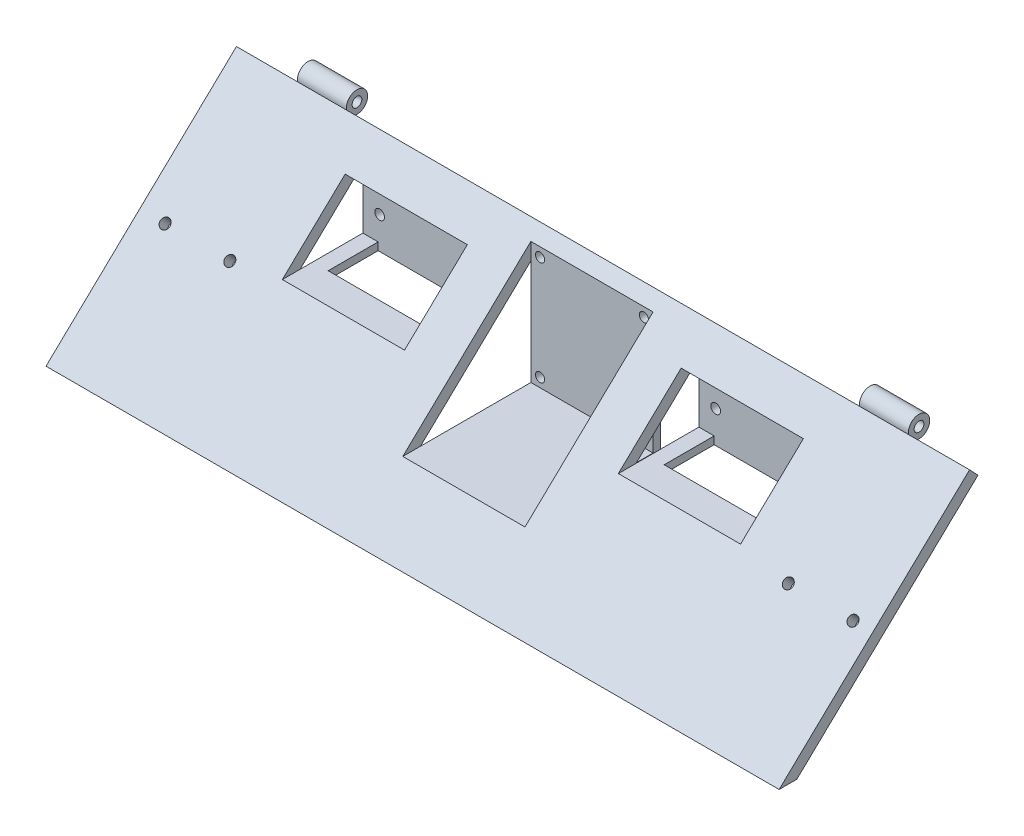
SolidWorks part; units mm, degrees
ref_plane "前视基准面" through (0, 0, 0) normal (0, 0, 1) x (1, 0, 0)
ref_plane "上视基准面" through (0, 0, 0) normal (0, 1, 0) x (1, 0, 0)
ref_plane "右视基准面" through (0, 0, 0) normal (1, 0, 0) x (0, 0, -1)
other "Configuration Table"
sketch "草图1" plane through (0, 0, 0) normal (1, 0, 0) x (0, 0, -1)
  line L0 (0, 0) -> (-23.9796, -22.8749) construction
  line L1 (-62.761, -57.1057) -> (-3.4588, -0.5354)
  line L2 (-62.761, -57.1057) -> (-60, -60)
  line L3 (-3.4588, -0.5354) -> (-0.6978, -3.4297)
  line L4 (-60, -60) -> (-0.6978, -3.4297)
  line L5 (-62.761, -57.1057) -> (-0.6978, -3.4297) construction
  line L6 (-3.4588, -0.5354) -> (-60, -60) construction
  line L7 (-62.761, -57.1057) -> (-65.7951, -60)
  line L8 (-65.7951, -60) -> (-60, -60)
  circle A0 centre (0, 0) radius 3.5
  circle A1 centre (0, 0) radius 1.6
  point P4 (-61.3805, -58.5528)
  point P6 (-31.7294, -30.2677)
  point P7 (-2.0783, -1.9826)
  point P8 (-58.5448, -35.4074)
  point P14 (0, 0)
  point P15 (-47.3852, -40.6579)
  point P16 (-52.4892, -28.6998)
  point P19 (-98.1791, -60)
  dimension "D1" = 3.2
  dimension "D2" = 7
  dimension "D3" = 4
  dimension "D4" = 60
  dimension "D5" = 60
extrude "凸台-拉伸1" add sketch "草图1" along normal blind 120 and the other way blind 120 contours A0 L1 L2 L4 | L7 L8 L2 | L3 A0 region at (0, -30.4148, 31.8836) region at (0, -59.0352, 62.852) region at (0, -2.1573, 2.2615)
extrude "凸台-拉伸2" add sketch "草图1<5>" along normal blind 16 from offset 84 contours L3 A0 A1 region at (0, 3.391, 0.2609)
sketch "草图1<5>" plane through (0, 0, 0) normal (1, 0, 0) x (0, 0, -1) same geometry as "草图1"
mirror "镜向1" about plane through (0, 0, 0) normal (1, 0, 0) of "凸台-拉伸2"
sketch "草图2" plane through (0, 0, 0) normal (1, 0, 0) x (0, 0, -1)
  line L0 (-7.0686, -3.9789) -> (-7.0686, -43.9789)
  line L1 (-7.0686, -43.9789) -> (-49.0003, -43.9789)
  line L2 (-0.6978, -3.4297) -> (-3.6169, -6.2144)
  line L3 (-49.0003, -43.9789) -> (-51.621, -46.4789)
  line L4 (-60, -60) -> (-0.6978, -3.4297)
  line L5 (-0.6978, -3.4297) -> (-3.4588, -0.5354)
  line L6 (-3.4588, -0.5354) -> (-65.7951, -60)
  line L7 (-65.7951, -60) -> (-60, -60)
  line L8 (-60, -60) -> (-0.6978, -3.4297)
  line L9 (-0.6978, -3.4297) -> (-3.4588, -0.5354)
  line L10 (-3.4588, -0.5354) -> (-65.7951, -60)
  line L11 (-65.7951, -60) -> (-60, -60)
  line L12 (-51.621, -46.4789) -> (-4.5686, -46.4789)
  line L13 (-4.5686, -46.4789) -> (-4.5686, -1.5941)
  line L14 (-4.5686, -1.5941) -> (-3.4588, -0.5354)
  point P6 (0, 0)
  point P12 (0, 0)
  dimension "D2" = 40
  dimension "D3" = 2.5
  dimension "D4" = 2.5
  dimension "D1" = 0
extrude "凸台-拉伸3" add sketch "草图2" along normal blind 20 and the other way blind 20 contours L12 L13 L8 L0 L1 region at (0, -8.7272, 5.425)
sketch "草图3" plane through (0, 0, 7.0686) normal (0, 0, 1) x (1, 0, 0)
  line L1 (-20, -43.9789) -> (20, -43.9789)
  line L2 (-20, -43.9789) -> (-20, -3.9789)
  line L3 (-20, -3.9789) -> (20, -3.9789)
  line L4 (-20, -43.9789) -> (20, -43.9789)
  line L5 (20, -43.9789) -> (20, -9.507)
  line L6 (20, -9.507) -> (-20, -9.507)
  line L7 (-20, -9.507) -> (-20, -43.9789)
  line L8 (-20, -43.9789) -> (20, -43.9789)
  line L9 (20, -43.9789) -> (20, -9.507)
  line L10 (20, -9.507) -> (-20, -9.507)
  line L11 (-20, -9.507) -> (-20, -43.9789)
  line L12 (20, -43.9789) -> (20, -3.9789)
  line M7 (-20, -43.9789) -> (20, -43.9789)
  line M8 (20, -43.9789) -> (20, -9.507)
  line M9 (20, -9.507) -> (-20, -9.507)
  line M10 (-20, -9.507) -> (-20, -43.9789)
  dimension "D2" = 40
  dimension "D1" = 0
extrude "切除-拉伸1" cut sketch "草图3" along normal up to surface (41.9317 mm away) contours M10 M7 M8 M9 | L12 L3 L2 M9 region at (0, -26.743, 7.0686) region at (0, -6.743, 7.0686) up to face at (0, -15.4016, 19.0429)
sketch "草图4" plane through (0, 0, 7.0686) normal (0, 0, 1) x (1, 0, 0)
  line L0 (0, -3.9789) -> (0, -43.9789) construction
  line L1 (0, -23.9789) -> (20, -23.9789) construction
  line L6 (-20, -43.9789) -> (20, -43.9789)
  line L7 (20, -43.9789) -> (20, -9.507)
  line L8 (20, -9.507) -> (20, -3.9789)
  line L9 (20, -3.9789) -> (-20, -3.9789)
  line L10 (-20, -3.9789) -> (-20, -9.507)
  line L11 (-20, -9.507) -> (-20, -43.9789)
  line L12 (-20, -43.9789) -> (20, -43.9789)
  line L13 (20, -43.9789) -> (20, -9.507)
  line L14 (20, -9.507) -> (20, -3.9789)
  line L15 (20, -3.9789) -> (-20, -3.9789)
  line L16 (-20, -3.9789) -> (-20, -9.507)
  line L17 (-20, -9.507) -> (-20, -43.9789)
  circle A0 centre (-17, -6.9789) radius 1.5
  circle A1 centre (17, -6.9789) radius 1.5
  circle A2 centre (-17, -40.9789) radius 1.5
  circle A3 centre (17, -40.9789) radius 1.5
  point P20 (14.0664, -3.9789)
  dimension "D2" = 3
  dimension "D3" = 3
  dimension "D4" = 3
  dimension "D1" = 0
extrude "切除-拉伸2" cut sketch "草图4" against normal through all contours A0 | A1 | A3 | A2 region at (-17, -6.9789, 7.0686) region at (17, -6.9789, 7.0686) region at (-17, -40.9789, 7.0686) region at (17, -40.9789, 7.0686)
sketch "草图5" plane through (0, 0, 0) normal (1, 0, 0) x (0, 0, -1)
  line L0 (-60, -60) -> (-0.6978, -3.4297) construction
  line L1 (-60, -60) -> (-0.6978, -3.4297)
  line L2 (-4.5686, -31.6222) -> (-30.2517, -31.6222)
  line L3 (-4.5686, -29.1222) -> (-27.631, -29.1222)
  line L6 (-45.8259, -46.4789) -> (-4.5686, -46.4789)
  line L7 (-4.5686, -46.4789) -> (-4.5686, -7.1222)
  line L8 (-4.5686, -7.1222) -> (-7.0686, -9.507)
  line L9 (-7.0686, -9.507) -> (-7.0686, -43.9789)
  line L10 (-7.0686, -43.9789) -> (-43.2052, -43.9789)
  line L11 (-43.2052, -43.9789) -> (-45.8259, -46.4789)
  line L12 (-45.8259, -46.4789) -> (-4.5686, -46.4789)
  line L13 (-4.5686, -46.4789) -> (-4.5686, -7.1222)
  line L14 (-4.5686, -7.1222) -> (-7.0686, -9.507)
  line L15 (-7.0686, -9.507) -> (-7.0686, -43.9789)
  line L16 (-7.0686, -43.9789) -> (-43.2052, -43.9789)
  line L17 (-43.2052, -43.9789) -> (-45.8259, -46.4789)
  dimension "D2" = 2.5
  dimension "D3" = 22
  dimension "D1" = 0
extrude "凸台-拉伸4" add sketch "草图5" along normal blind 40 from offset 35 contours L15 L3 L1 L2 | L1 L15 L3 L13 | L3 L15 L2 L13 region at (0, -30.3971, 18.0181) region at (0, -30.3722, 5.8186) region at (0, -18.707, 5.7947)
sketch "草图6" plane through (0, 0, 7.0686) normal (0, 0, 1) x (1, 0, 0)
  line L4 (35, -9.507) -> (35, -29.1222)
  line L5 (35, -29.1222) -> (75, -29.1222)
  line L6 (75, -29.1222) -> (75, -9.507)
  line L7 (75, -9.507) -> (35, -9.507)
  line L8 (35, -9.507) -> (35, -29.1222)
  line L9 (35, -29.1222) -> (75, -29.1222)
  line L10 (75, -29.1222) -> (75, -9.507)
  line L11 (75, -9.507) -> (35, -9.507)
  dimension "D1" = 0
extrude "切除-拉伸3" cut sketch "草图6" along normal up to surface (26.3575 mm away) up to face at (0, -15.4016, 19.0429)
sketch "草图7" plane through (0, -29.1222, 0) normal (0, 1, 0) x (1, 0, 0)
  line L1 (40, -7.0686) -> (70, -7.0686)
  line L2 (40, -7.0686) -> (40, -23.4261)
  line L3 (40, -23.4261) -> (70, -23.4261)
  line L4 (70, -7.0686) -> (70, -23.4261)
  line L6 (35, -7.0686) -> (35, -27.631)
  line L7 (35, -27.631) -> (35, -33.4261)
  line L8 (35, -33.4261) -> (75, -33.4261)
  line L9 (75, -33.4261) -> (75, -27.631)
  line L10 (75, -27.631) -> (75, -7.0686)
  line L11 (75, -7.0686) -> (35, -7.0686)
  line L12 (35, -7.0686) -> (35, -27.631)
  line L13 (35, -27.631) -> (35, -33.4261)
  line L14 (35, -33.4261) -> (75, -33.4261)
  line L15 (75, -33.4261) -> (75, -27.631)
  line L16 (75, -27.631) -> (75, -7.0686)
  line L17 (75, -7.0686) -> (35, -7.0686)
  line M15 (75, -7.0686) -> (35, -7.0686)
  dimension "D2" = 5
  dimension "D3" = 5
  dimension "D4" = 10
  dimension "D1" = 0
extrude "切除-拉伸4" cut sketch "草图7" against normal up to surface (2.5 mm away) contours L4 L2 L3 M15 region at (55, -29.1222, 15.2473) up to face at (55, -31.6222, 17.4102)
sketch "草图8" plane through (0, 0, 7.0686) normal (0, 0, 1) x (1, 0, 0)
  line L0 (55, -9.507) -> (55, -31.6222) construction
  line L8 (35, -9.507) -> (35, -29.1222)
  line L9 (35, -29.1222) -> (40, -29.1222)
  line L10 (40, -29.1222) -> (40, -31.6222)
  line L11 (40, -31.6222) -> (70, -31.6222)
  line L12 (70, -31.6222) -> (70, -29.1222)
  line L13 (70, -29.1222) -> (75, -29.1222)
  line L14 (75, -29.1222) -> (75, -9.507)
  line L15 (75, -9.507) -> (35, -9.507)
  line L16 (35, -9.507) -> (35, -29.1222)
  line L17 (35, -29.1222) -> (40, -29.1222)
  line L18 (40, -29.1222) -> (40, -31.6222)
  line L19 (40, -31.6222) -> (70, -31.6222)
  line L20 (70, -31.6222) -> (70, -29.1222)
  line L21 (70, -29.1222) -> (75, -29.1222)
  line L22 (75, -29.1222) -> (75, -9.507)
  line L23 (75, -9.507) -> (35, -9.507)
  circle A0 centre (40.5, -21.1222) radius 1.6
  circle A1 centre (69.5, -21.1222) radius 1.6
  dimension "D2" = 3.2
  dimension "D3" = 29
  dimension "D4" = 8
  dimension "D1" = 0
extrude "切除-拉伸5" cut sketch "草图8" against normal up to surface (2.5 mm away) contours A0 | A1 region at (40.5, -21.1222, 7.0686) region at (69.5, -21.1222, 7.0686) up to face at (55, -19.3722, 4.5686)
mirror "镜向2" about plane through (0, 0, 0) normal (1, 0, 0) of "凸台-拉伸4"
mirror "镜向3" about plane through (0, 0, 0) normal (1, 0, 0) of "切除-拉伸4"
mirror "镜向4" about plane through (0, 0, 0) normal (1, 0, 0) of "切除-拉伸5"
mirror "镜向5" about plane through (0, 0, 0) normal (1, 0, 0) of "切除-拉伸3"
sketch "草图9" plane through (0, -1.4472, -1.3805) normal (0, -0.7236, -0.6902) x (1, 0, 0)
  line L0 (0.9143, 84.8292) -> (0.9143, 2.8723) construction
  line L2 (102.9143, 29.8292) -> (102.9143, 49.8292) construction
  line L3 (118.4143, 29.8292) -> (87.4143, 29.8292) construction
  line L4 (118.4143, 29.8292) -> (118.4143, 49.8292) construction
  line L5 (118.4143, 49.8292) -> (87.4143, 49.8292) construction
  line L6 (87.4143, 29.8292) -> (87.4143, 49.8292) construction
  line L8 (-120, 2.8723) -> (-100, 2.8723)
  line L9 (-100, 2.8723) -> (-84, 2.8723)
  line L10 (-84, 2.8723) -> (84, 2.8723)
  line L11 (84, 2.8723) -> (100, 2.8723)
  line L12 (100, 2.8723) -> (120, 2.8723)
  line L13 (120, 2.8723) -> (120, 84.8292)
  line L14 (120, 84.8292) -> (-120, 84.8292)
  line L15 (-120, 84.8292) -> (-120, 2.8723)
  line L16 (-120, 2.8723) -> (-100, 2.8723)
  line L17 (-100, 2.8723) -> (-84, 2.8723)
  line L18 (-84, 2.8723) -> (84, 2.8723)
  line L19 (84, 2.8723) -> (100, 2.8723)
  line L20 (100, 2.8723) -> (120, 2.8723)
  line L21 (120, 2.8723) -> (120, 84.8292)
  line L22 (120, 84.8292) -> (-120, 84.8292)
  line L23 (-120, 84.8292) -> (-120, 2.8723)
  circle A0 centre (113.5112, 46.6292) radius 1.6
  circle A1 centre (92.3174, 46.6292) radius 1.6
  circle A2 centre (-90.4888, 46.6292) radius 1.6
  circle A3 centre (-111.6826, 46.6292) radius 1.6
  point P20 (75.5314, 63.7755)
  dimension "D4" = 3.2
  dimension "D2" = 31
  dimension "D3" = 20
  dimension "D5" = 3.2
  dimension "D6" = 102
  dimension "D7" = 35
  dimension "D1" = 0
extrude "切除-拉伸6" cut sketch "草图9" against normal up to surface (4 mm away) contours A0 | A1 | A2 | A3 region at (113.5112, -33.6327, 32.3594) region at (92.3174, -33.6327, 32.3594) region at (-90.4888, -33.6327, 32.3594) region at (-111.6826, -33.6327, 32.3594) up to face at (-55, -19.3146, 23.1449)
